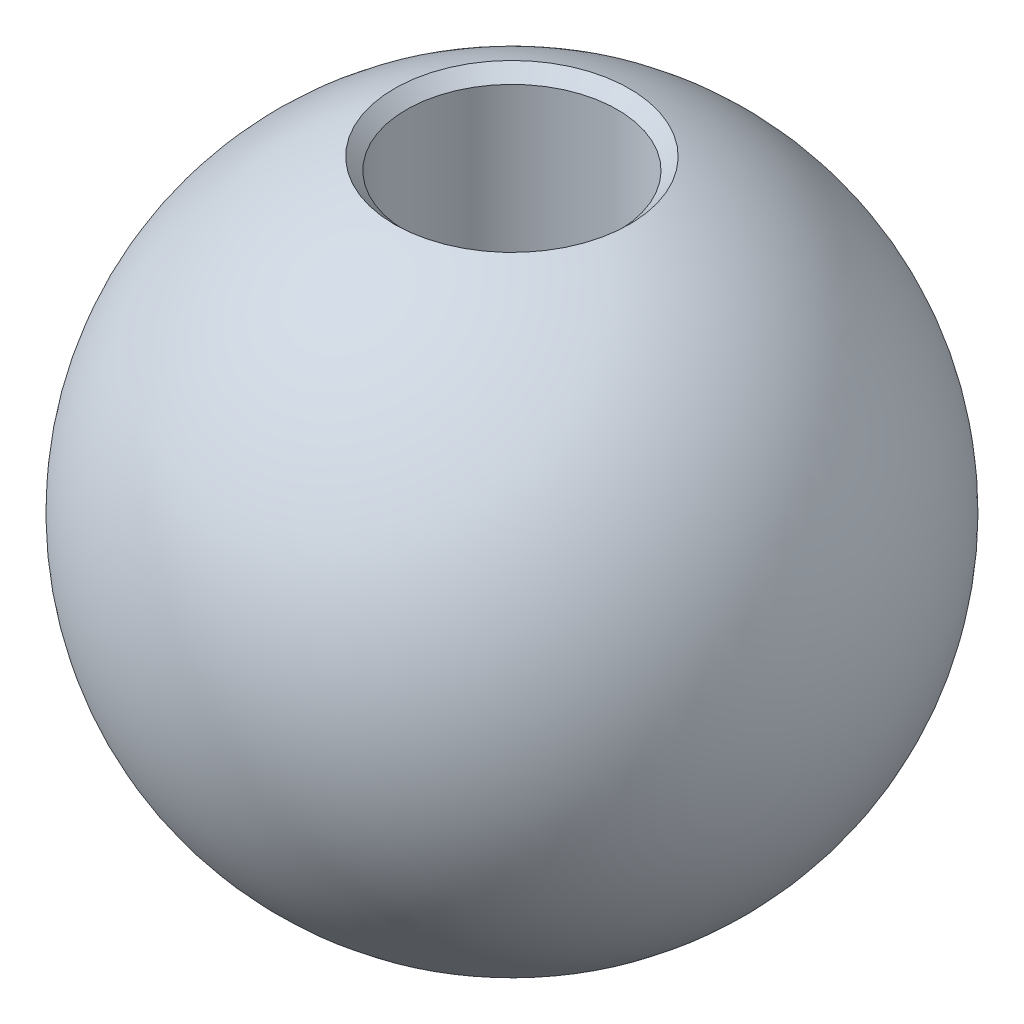
SolidWorks part; units mm, degrees
ref_plane "Front Plane" through (0, 0, 0) normal (0, 0, 1) x (1, 0, 0)
ref_plane "Top Plane" through (0, 0, 0) normal (0, 1, 0) x (1, 0, 0)
ref_plane "Right Plane" through (0, 0, 0) normal (1, 0, 0) x (0, 0, -1)
sketch "Sketch1" plane through (0, 0, 0) normal (0, 0, 1) x (1, 0, 0)
  line L0 (-5, 0) -> (5, 0) construction
  point P4 (0, 0)
  dimension "Diameter" = 10
sketch "Sketch2" plane through (0, 0, 0) normal (0, 0, 1) x (1, 0, 0)
  line L0 (-5, 0) -> (5, 0)
  arc A1 (5, 0) -> (-5, 0) centre (0, 0) ccw
revolve "Revolve1" add sketch "Sketch2" angle 360 about L0
ref_plane "Plane1" through (0, 5, 0) normal (0, 1, 0) x (1, 0, 0)
hole_wizard "M3 Clearance Hole1" positions "Sketch3" profile "Sketch4" hole size "M3" standard "ANSI Metric" end condition through all
sketch "Sketch3" plane through (0, 5, 0) normal (0, 1, 0) x (1, 0, 0)
  point P0 (0, 0)
sketch "Sketch4" plane through (0, 5, 0) normal (1, 0, 0) x (0, 0, 1)
  line L0 (0, 0) -> (0, 10)
  line L1 (0, 10) -> (1.6, 10)
  line L2 (1.6, 10) -> (1.6, 0)
  line L5 (1.6, 0) -> (0, 0)
  line L11 (0, -6.35) -> (0, 107.95) construction
  dimension "Thru Hole Dia." = 3.2
  dimension "Thru Hole Depth" = 10
chamfer "Chamfer1" distance 0.25 angle 45 2 edges at (0, 4.7371, -1.6) (0, -4.7371, 1.6) first distance on face at (0, -4.7371, 1.6)
